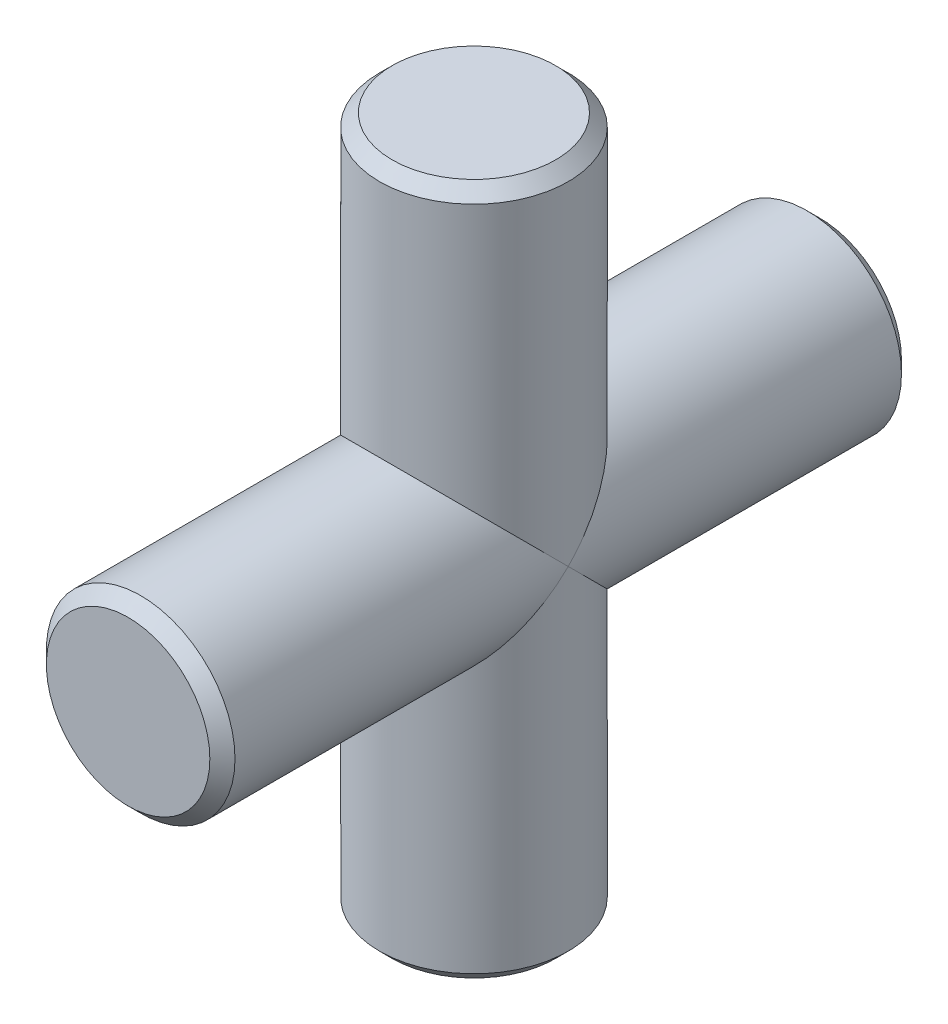
SolidWorks part; units mm, degrees
ref_plane "前视基准面" through (0, 0, 0) normal (0, 0, 1) x (1, 0, 0)
ref_plane "上视基准面" through (0, 0, 0) normal (0, 1, 0) x (1, 0, 0)
ref_plane "右视基准面" through (0, 0, 0) normal (1, 0, 0) x (0, 0, -1)
sketch "草图1" plane through (0, 0, 0) normal (0, 1, 0) x (1, 0, 0)
  circle A0 centre (0, 0) radius 1.5
  dimension "D1" = 3
extrude "凸台-拉伸1" add sketch "草图1" along normal blind 11
sketch "草图2" plane through (0, 0, 0) normal (0, 0, 1) x (1, 0, 0)
  line L0 (-1.5, 0) -> (1.5, 0) construction
  circle A0 centre (0, 5.5) radius 1.5
  dimension "D1" = 3
  dimension "D2" = 5.5
extrude "凸台-拉伸2" add sketch "草图2" along normal mid plane 11
chamfer "倒角1" distance 0.2 angle 45 4 edges at (1.5, 5.5, 5.5) (0, 0, 1.5) (1.5, 5.5, -5.5) (0, 11, 1.5)
ref_axis "基准轴1" through (0, 5.5, 0) along (0, 0, -1)
ref_plane "基准面1" through (0, 5.5, 0) normal (0, 1, 0) x (1, 0, 0)
